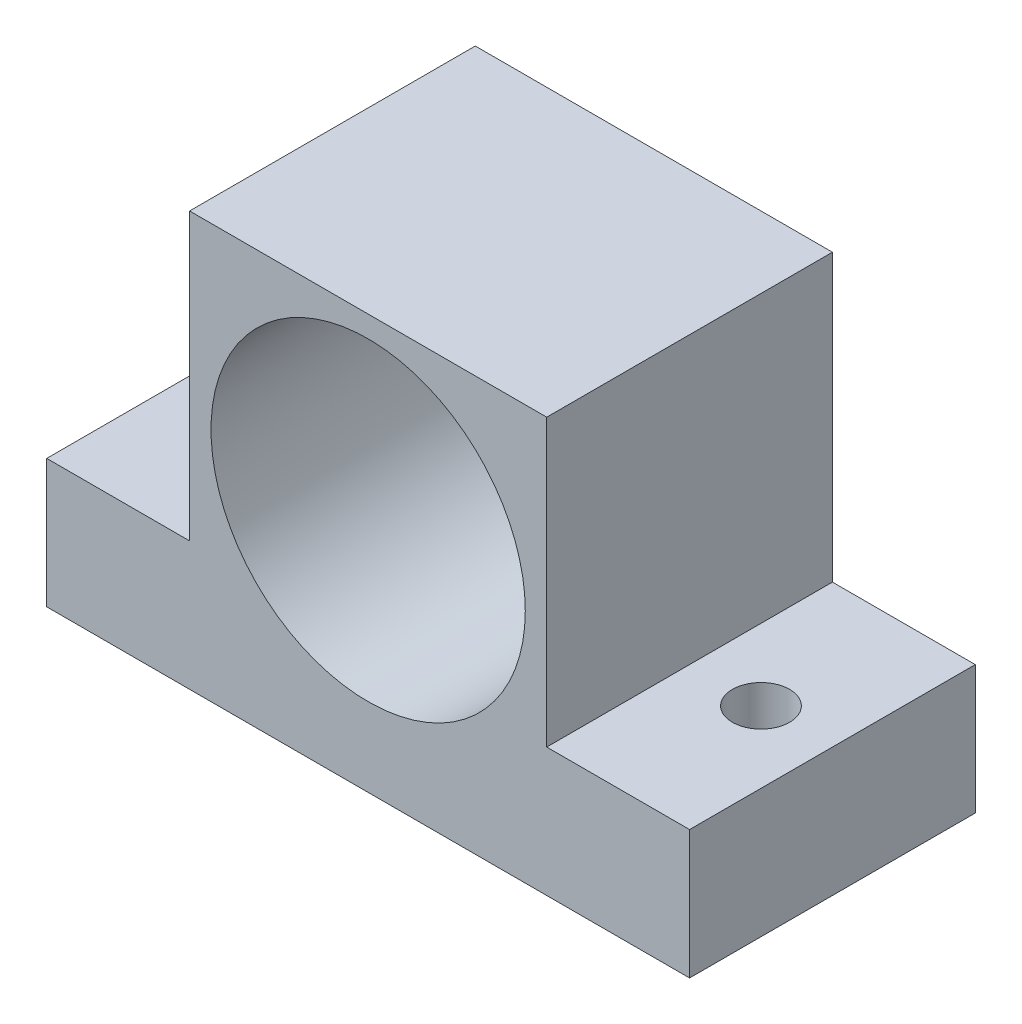
SolidWorks part; units mm, degrees
material "ABS"
ref_plane "Front Plane" through (0, 0, 0) normal (0, 0, 1) x (1, 0, 0)
ref_plane "Top Plane" through (0, 0, 0) normal (0, 1, 0) x (1, 0, 0)
ref_plane "Right Plane" through (0, 0, 0) normal (1, 0, 0) x (0, 0, -1)
sketch "Sketch1" plane through (0, 0, 0) normal (0, 0, 1) x (1, 0, 0)
  line L1 (-12.5, 12.5) -> (12.5, 12.5)
  line L2 (-12.5, 12.5) -> (-12.5, -16.5)
  line L3 (-12.5, -16.5) -> (12.5, -16.5)
  line L4 (12.5, 12.5) -> (12.5, -16.5)
  line L5 (-12.5, 12.5) -> (12.5, -16.5) construction
  line L6 (-12.5, -16.5) -> (12.5, 12.5) construction
  line L7 (12.5, -16.5) -> (22.5, -16.5)
  line L8 (12.5, -16.5) -> (12.5, -7.5)
  line L9 (12.5, -7.5) -> (22.5, -7.5)
  line L10 (22.5, -16.5) -> (22.5, -7.5)
  line L11 (12.5, -16.5) -> (22.5, -7.5) construction
  line L12 (12.5, -7.5) -> (22.5, -16.5) construction
  line L13 (-12.5, -16.5) -> (-22.5, -16.5)
  line L14 (-12.5, -16.5) -> (-12.5, -7.5)
  line L15 (-12.5, -7.5) -> (-22.5, -7.5)
  line L16 (-22.5, -16.5) -> (-22.5, -7.5)
  line L17 (-12.5, -16.5) -> (-22.5, -7.5) construction
  line L18 (-12.5, -7.5) -> (-22.5, -16.5) construction
  circle A0 centre (0, 0) radius 4.1
  circle A1 centre (0, 0) radius 11
  point P8 (0, 0)
  point P14 (17.5, -12)
  point P16 (-17.5, -12)
  dimension "D4" = 8.2
  dimension "D5" = 22
  dimension "D1" = 12.5
  dimension "D2" = 29
  dimension "D3" = 25
  dimension "D6" = 10
  dimension "D7" = 9
  dimension "D8" = 10
  dimension "D9" = 9
  dimension "D10" = 12.5
extrude "Boss-Extrude1" add sketch "Sketch1" along normal blind 20 contours L4 L1 L2 L3 A1 | L16 L13 L2 L15 | L7 L10 L9 L4 region at (0, 12.1171, 0) region at (-17.5, -12, 0) region at (17.5, -12, 0)
sketch "Sketch2" plane through (0, -7.5, 0) normal (0, 1, 0) x (1, 0, 0)
  line L0 (-22.5, 0) -> (-12.5, -20)
  line L1 (-12.5, -20) -> (-22.5, -20)
  line L2 (-22.5, -20) -> (-12.5, 0)
  line L3 (12.5, 0) -> (22.5, -20)
  line L4 (22.5, -20) -> (22.5, 0)
  line L5 (22.5, 0) -> (12.5, -20)
  circle A0 centre (-17.5, -10) radius 2
  circle A1 centre (17.5, -10) radius 2
  dimension "D1" = 4
  dimension "D2" = 4
extrude "Cut-Extrude1" cut sketch "Sketch2" against normal blind 9 contours L0 A0 L2 | L2 A0 L0 | L0 A0 L2 | L2 A0 L0 | A1 region at (-17.5, -7.5, 8.7139) region at (-18.5772, -7.5, 10) region at (-16.4228, -7.5, 10) region at (-17.5, -7.5, 11.2861)
